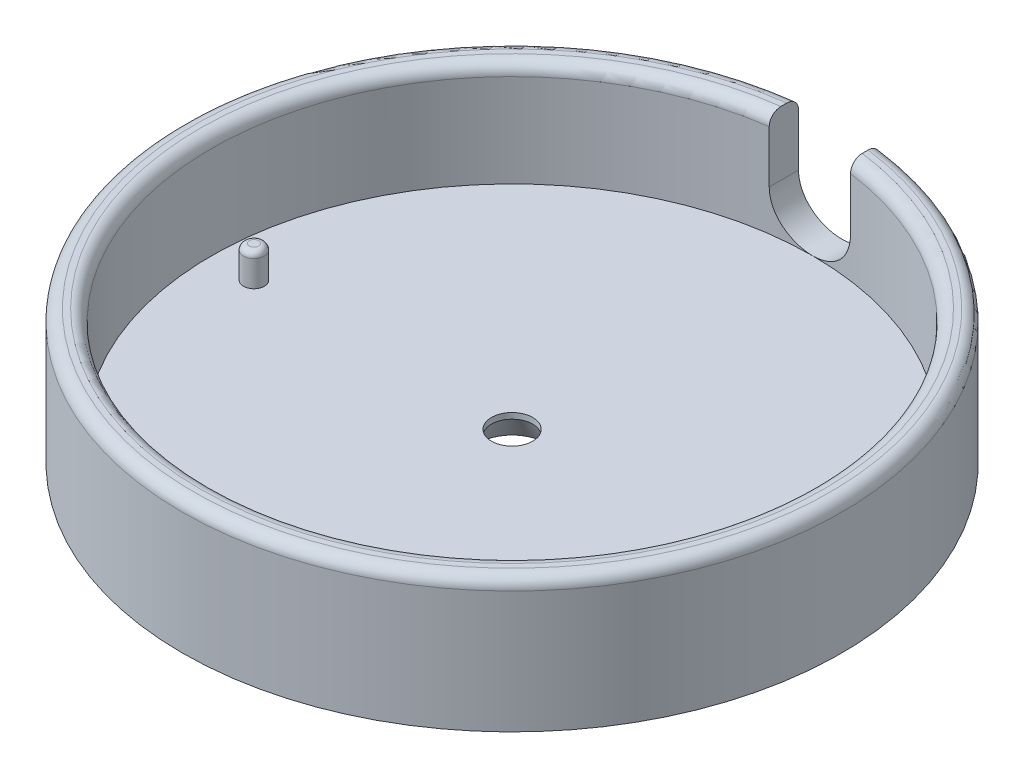
SolidWorks part; units mm, degrees
ref_plane "Front Plane" through (0, 0, 0) normal (0, 0, 1) x (1, 0, 0)
ref_plane "Top Plane" through (0, 0, 0) normal (0, 1, 0) x (1, 0, 0)
ref_plane "Right Plane" through (0, 0, 0) normal (1, 0, 0) x (0, 0, -1)
sketch "Sketch1" plane through (0, 0, 0) normal (0, 1, 0) x (1, 0, 0)
  circle A0 centre (0, 0) radius 56.75
extrude "Boss-Extrude3" add sketch "Sketch1" along normal blind 23
sketch "Sketch10" plane through (0, 23, 0) normal (0, 1, 0) x (1, 0, 0)
  circle A0 centre (0, 0) radius 51.75
extrude "Cut-Extrude3" cut sketch "Sketch10" against normal blind 18
sketch "Sketch12" plane through (0, 5, 0) normal (0, 1, 0) x (1, 0, 0)
  circle A0 centre (0, 0) radius 3.55
extrude "Cut-Extrude4" cut sketch "Sketch12" against normal through all
sketch "Sketch14" plane through (0, 5, 0) normal (0, 1, 0) x (1, 0, 0)
  line L0 (0, 0) -> (-44.45, 0)
sketch "Sketch16" plane through (0, 5, 0) normal (0, 1, 0) x (1, 0, 0)
  line L0 (0, 0) -> (44.45, 0)
sketch "Sketch17" plane through (0, 5, 0) normal (0, 1, 0) x (1, 0, 0)
  circle A0 centre (-44.45, 0) radius 1.8
sketch "Sketch18" plane through (0, 5, 0) normal (0, 1, 0) x (1, 0, 0)
  circle A0 centre (44.45, 0) radius 1.8
extrude "Boss-Extrude4" add sketch "Sketch17" along normal blind 5.5 contours A0
extrude "Boss-Extrude5" add sketch "Sketch18" along normal blind 5.5 contours A0
fillet "Fillet5" radius 1 1 edges at (-44.45, 10.5, 1.8)
fillet "Fillet6" radius 1 1 edges at (44.45, 10.5, 1.8)
sketch3d "3DSketch3" plane through (0, 0, 0) normal (0, 0, 1) x (1, 0, 0)
  dimension "D1" = 54.25
sketch "Sketch26" plane through (0, 0, -54.25) normal (0, 0, 1) x (1, 0, 0)
  line L0 (0, 0) -> (0, 23)
sketch "Sketch27" plane through (0, 0, -54.25) normal (0, 0, 1) x (1, 0, 0)
  line L0 (0, 23) -> (0, 12) construction
  line L1 (0, 0) -> (0, 23) construction
  line L2 (7, 23) -> (7, 12)
  line L3 (-7, 23) -> (-7, 12)
  arc A0 (7, 23) -> (-7, 23) centre (0, 23) ccw
  arc A1 (-7, 12) -> (7, 12) centre (0, 12) ccw
  point P5 (0, 17.5)
extrude "Cut-Extrude5" cut sketch "Sketch27" against normal blind 3 and the other way blind 3 contours A0 L3 A1 L2
fillet "Fillet7" radius 2 1 edges at (0, 23, 51.75)
fillet "Fillet8" radius 2 1 edges at (0, 23, 56.75)
sketch "Sketch28" plane through (0, 0, 0) normal (0, 1, 0) x (1, 0, 0)
  circle A0 centre (0, 0) radius 5.85
chamfer "Chamfer1" distance 4 angle 30 1 edges at (0, 0, 3.55) first distance on face at (0, 0, 3.55)
